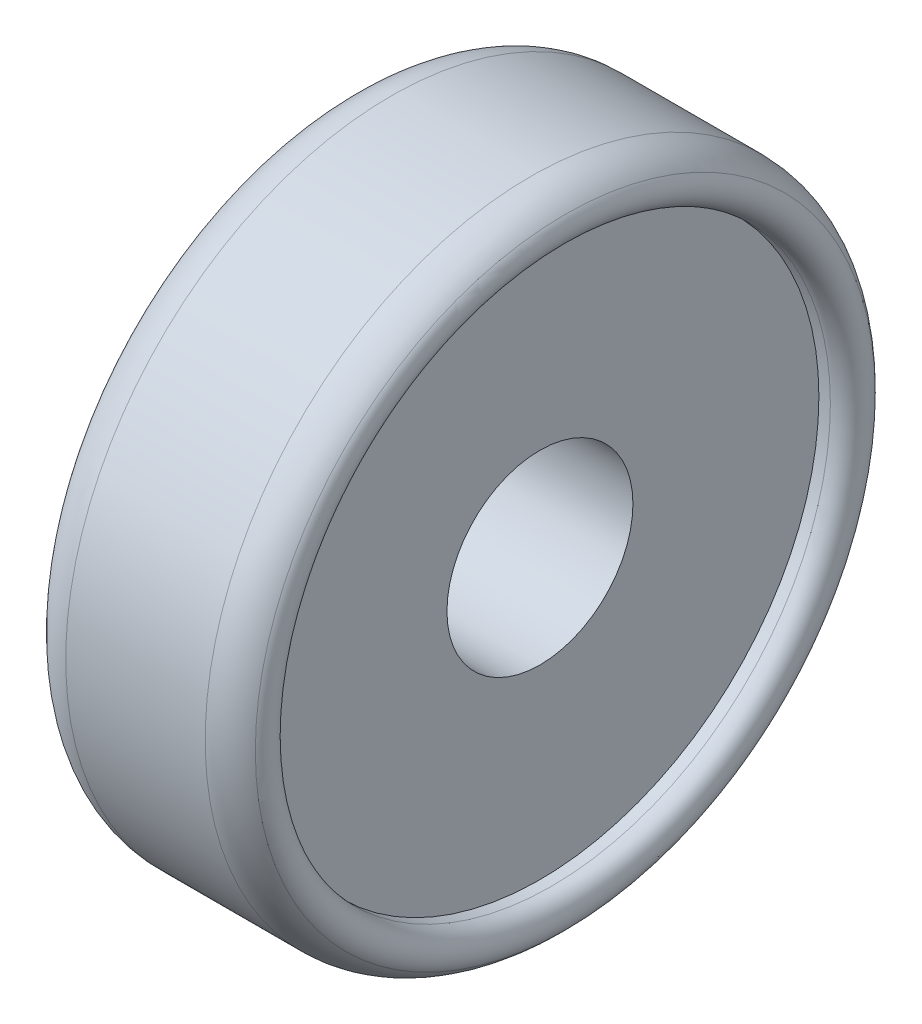
SolidWorks part; units mm, degrees
ref_plane "Front Plane" through (0, 0, 0) normal (0, 0, 1) x (1, 0, 0)
ref_plane "Top Plane" through (0, 0, 0) normal (0, 1, 0) x (1, 0, 0)
ref_plane "Right Plane" through (0, 0, 0) normal (1, 0, 0) x (0, 0, -1)
sketch "Sketch1" plane through (0, 0, 0) normal (1, 0, 0) x (0, 0, -1)
  circle A0 centre (0, 0) radius 100
  circle A1 centre (0, 0) radius 350
  dimension "D1" = 200
  dimension "D2" = 700
extrude "Boss-Extrude1" add sketch "Sketch1" along normal mid plane 250
fillet "Fillet1" radius 50 1 edges at (-125, 0, -350)
fillet "Fillet2" radius 50 1 edges at (125, 0, -350)
sketch "Sketch2" plane through (-125, 0, 0) normal (-1, 0, 0) x (0, 0, 1)
  circle A0 centre (0, 0) radius 300
  dimension "D1" = 600
extrude "Cut-Extrude1" cut sketch "Sketch2" against normal blind 40
sketch "Sketch4" plane through (125, 0, 0) normal (1, 0, 0) x (0, 0, -1)
  circle A0 centre (0, 0) radius 300
  dimension "D1" = 600
extrude "Cut-Extrude2" cut sketch "Sketch4" against normal blind 40
fillet "Fillet3" radius 20 1 edges at (125, 0, -300)
fillet "Fillet4" radius 20 1 edges at (-125, 0, 300)
